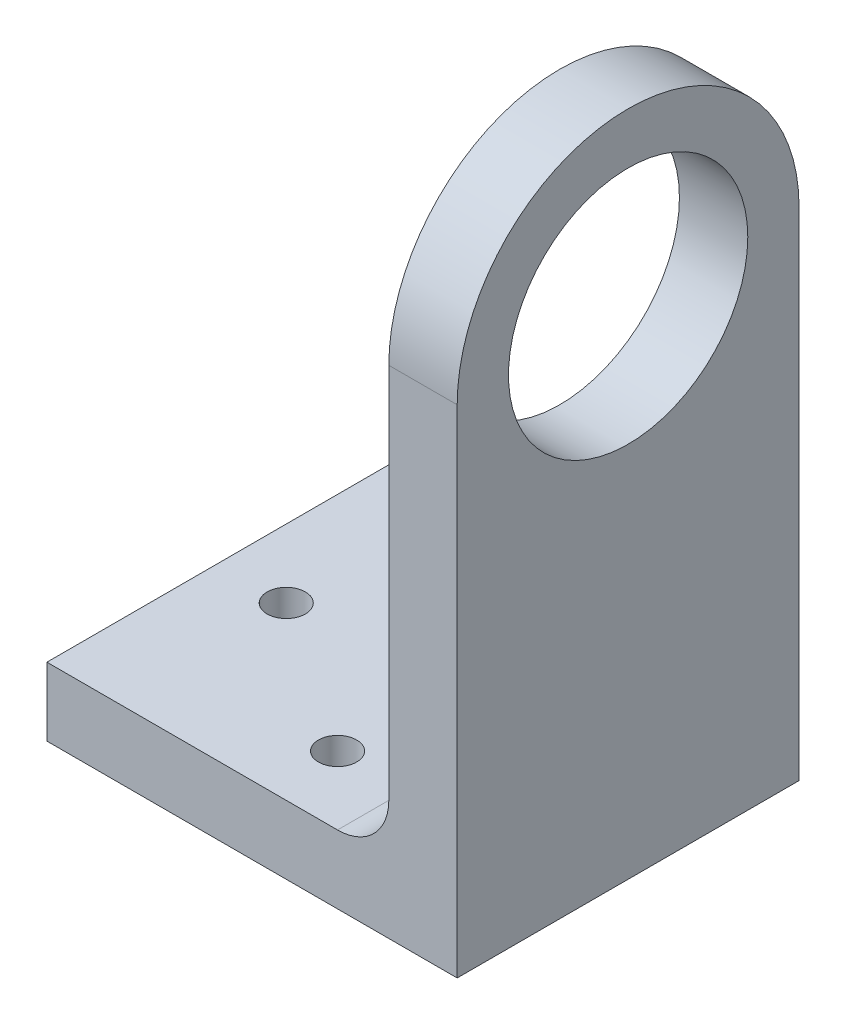
SolidWorks part; units mm, degrees
ref_plane "Front Plane" through (0, 0, 0) normal (0, 0, 1) x (1, 0, 0)
ref_plane "Top Plane" through (0, 0, 0) normal (0, 1, 0) x (1, 0, 0)
ref_plane "Right Plane" through (0, 0, 0) normal (1, 0, 0) x (0, 0, -1)
sketch "Sketch3" plane through (0, 0, 0) normal (1, 0, 0) x (0, 0, -1)
  line L1 (0, 0) -> (31.75, 0)
  line L2 (0, 0) -> (0, 39.75)
  line L4 (31.75, 0) -> (31.75, 39.75)
  circle A4 centre (15.875, 39.75) radius 11.1125
  arc A5 (0, 39.75) -> (31.75, 39.75) centre (15.875, 39.75) cw
  point P34 (15.875, 0)
  dimension "D4" = 22.225
  dimension "D1" = 39.75
  dimension "D2" = 31.75
extrude "Boss-Extrude1" add sketch "Sketch3" along normal blind 6.35
sketch "Sketch5" plane through (6.35, 0, 0) normal (1, 0, 0) x (0, 0, -1)
  line L1 (0, 0) -> (31.75, 0)
  line L2 (0, 0) -> (0, -6.35)
  line L3 (0, -6.35) -> (31.75, -6.35)
  line L4 (31.75, 0) -> (31.75, -6.35)
  dimension "D1" = 6.35
extrude "Boss-Extrude2" add sketch "Sketch5" against normal blind 38.1
fillet "Fillet1" radius 4.7625 1 edges at (0, 0, -15.875)
sketch "Sketch6" plane through (0, 0, 0) normal (0, 1, 0) x (1, 0, 0)
  line L0 (-31.75, 0) -> (-4.7625, 0) construction
  line L1 (-4.7625, 0) -> (-4.7625, 31.75) construction
  line L2 (-31.75, 31.75) -> (-31.75, 0) construction
  line L3 (0, 15.875) -> (-33.0413, 15.875) construction
  line L4 (0, 31.75) -> (0, 0) construction
  circle A0 centre (-11.1125, 6.35) radius 1.777
  circle A2 centre (-25.4, 15.875) radius 1.777
  circle A3 centre (-11.1125, 25.4) radius 1.777
  dimension "D1" = 3.554
  dimension "D2" = 6.35
  dimension "D3" = 6.35
  dimension "D4" = 6.35
extrude "Cut-Extrude1" cut sketch "Sketch6" against normal through all
equation "\"D1@Sketch6\" = 3.3mm + \"normtol\""
equation "\"tighttol\" = 0.005in"
equation "\"normtol\" = 0.01in"
equation "\"loosetol\" = 0.02in"
equation "\"Fry height\"= 0.5in"
equation "\"Fry spacing\"= 0.5625in"
equation "\"Potato width\"= \"Fry spacing\" * 4"
equation "\"Potato length\"= 80mm"
equation "\"top robot surface separation\" = 1/8+1/8+8mm"
equation "\"D1@Sketch3\"=1+\"top robot surface separation\""
